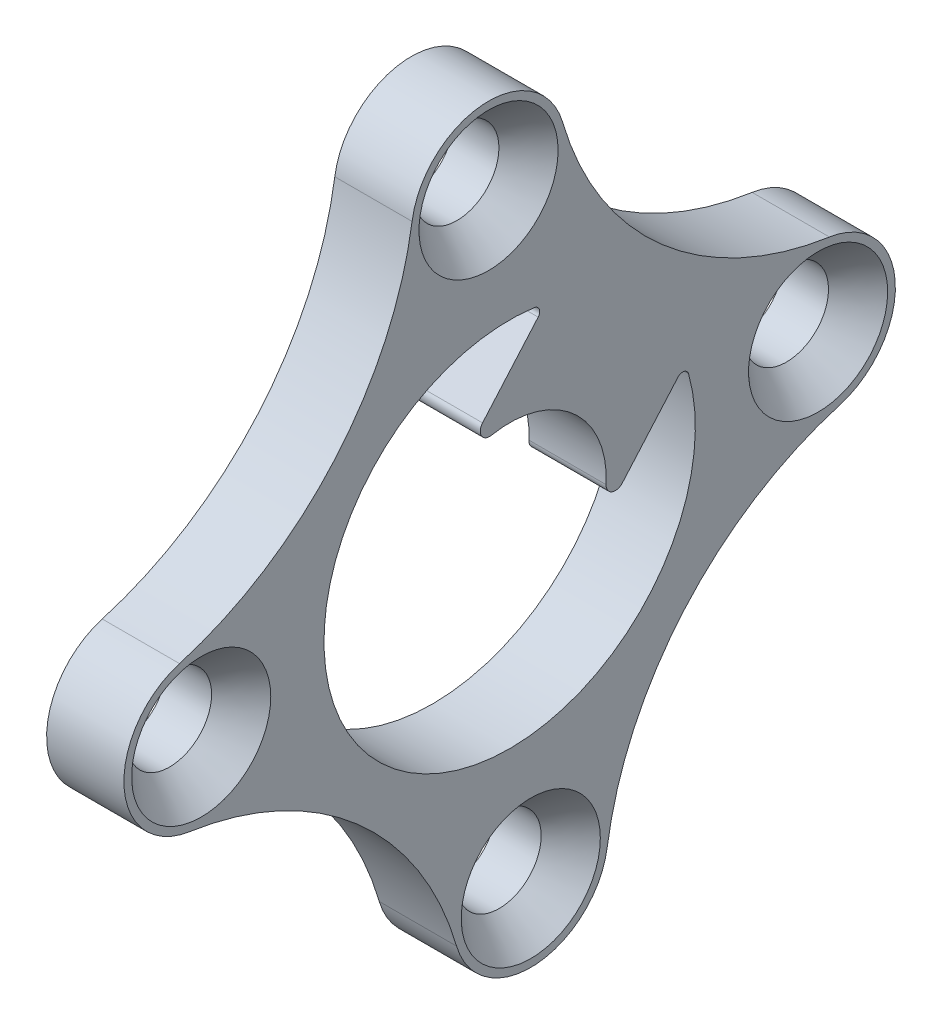
SolidWorks part; units mm, degrees
material "6061-T6 (SS)"
ref_plane "Front Plane" through (0, 0, 0) normal (0, 0, 1) x (1, 0, 0)
ref_plane "Top Plane" through (0, 0, 0) normal (0, 1, 0) x (1, 0, 0)
ref_plane "Right Plane" through (0, 0, 0) normal (1, 0, 0) x (0, 0, -1)
sketch "Sketch1" plane through (-42.315, 0, 0) normal (-1, 0, 0) x (0, 0, 1)
  line L0 (-1.1709, 7.1407) -> (1.1131, 4.521)
  line L1 (-2.2823, 8.4156) -> (-1.0705, 7.0256) construction
  line L2 (-4.6305, -0.4865) -> (-6.9145, 2.1332)
  line L3 (-8.0259, 3.4081) -> (-4.7496, -0.3499) construction
  line L5 (-1.0705, 7.0256) -> (2.1416, 3.3414) construction
  line L6 (12.6703, -0.8675) -> (-12.6703, 0.8675) construction
  line L7 (-0.8675, -12.6703) -> (0.8675, 12.6703) construction
  arc A0 (1.1131, 4.521) -> (0.7536, 3.8965) centre (0.8259, 4.2706) cw
  arc A1 (0.7536, 3.8965) -> (-3.9629, -0.2155) centre (0, 0) ccw
  arc A2 (-3.9629, -0.2155) -> (-4.6305, -0.4865) centre (-4.3433, -0.2361) cw
  circle A3 centre (0, 0) radius 3.9687 construction
  circle A4 centre (0, 0) radius 3.9687 construction
  arc A5 (-1.1709, 7.1407) -> (-1.0132, 7.5594) centre (-0.9794, 7.3077) cw
  arc A8 (-1.0132, 7.5594) -> (-7.3508, 2.0341) centre (0, 0) cw
  arc A9 (-7.3508, 2.0341) -> (-6.9145, 2.1332) centre (-7.106, 1.9663) cw
  circle A10 centre (0, 0) radius 15.875
  arc A11 (-7.2511, 1.916) -> (-0.9098, 7.4446) centre (0, 0) ccw construction
  circle A12 centre (0.8675, 12.6703) radius 3.175 construction
  circle A13 centre (0.8675, 12.6703) radius 2.6924 construction
  circle A14 centre (0, 0) radius 9.525 construction
  dimension "D1" = 0.381
  dimension "D2" = 0.254
  dimension "D3" = 25.4
  dimension "D4" = 0.127
  dimension "D6" = 5.3848
  dimension "D7" = 19.05
  dimension "D5" = 45
extrude "Boss-Extrude1" add sketch "Sketch1" against normal blind 3.175
sketch "Sketch2" plane through (-42.315, 0, 0) normal (-1, 0, 0) x (0, 0, 1)
  line L0 (-0.8675, -12.6703) -> (0.8675, 12.6703) construction
  line L1 (-1.1709, 7.1407) -> (1.1131, 4.521) construction
  line L2 (7.1795, 6.2594) -> (11.9659, 10.4323)
  arc A0 (1.0844, 15.8379) -> (11.9659, 10.4323) centre (0, 0) cw
  circle A1 centre (0, 0) radius 15.875 construction
  circle A3 centre (0, 0) radius 9.525 construction
  arc A5 (4.0082, 13.136) -> (1.0844, 15.8379) centre (0.8675, 12.6703) ccw
  circle A6 centre (0.8675, 12.6703) radius 3.175 construction
  arc A7 (4.0082, 13.136) -> (7.1795, 6.2594) centre (17.3329, 15.1115) ccw
extrude "Cut-Extrude1" cut sketch "Sketch2" against normal through all
mirror "Mirror1" about plane through (-39.14, 6.2594, 7.1795) normal (0, -0.7538, 0.6572) of "Cut-Extrude1"
pattern_circular "CirPattern2" count 4 over 360 about axis through (-42.315, 0, 0) along (-1, 0, 0) of "Cut-Extrude1", "Mirror1"
hole_wizard "CSK for #4 Flat Head Machine Screw1" positions "Sketch3" profile "Sketch4" countersink size "#4" standard "ANSI Inch" end condition up to next
sketch "Sketch3" plane through (-39.14, 0, 0) normal (1, 0, 0) x (0, 0, -1)
  point P0 (12.6703, 0.8675)
  point P3 (12.6703, 0.8675)
  point P6 (12.6703, 0.8675)
  point P9 (12.6703, 0.8675)
  point P13 (-0.8675, 12.6703)
  point P16 (-12.6703, -0.8675)
  point P19 (0.8675, -12.6703)
sketch "Sketch4" plane through (-39.14, 0.8675, -12.6703) normal (0, 1, 0) x (0, 0, -1)
  line L0 (0, 0) -> (0, 3.175)
  line L1 (0, 3.175) -> (1.7272, 3.175)
  line L2 (1.7272, 3.175) -> (1.7272, 1.3003)
  line L3 (1.7272, 1.3003) -> (2.8575, 0)
  line L5 (2.8575, 0) -> (0, 0)
  line L6 (-1.7272, 1.3003) -> (-2.8575, 0) construction
  line L11 (0, -6.35) -> (0, 107.95) construction
  dimension "Thru Hole Dia." = 3.4544
  dimension "Thru Hole Depth" = 3.175
  dimension "Near C'Sink Dia." = 5.715
  dimension "Near C'Sink Angle" = 82
